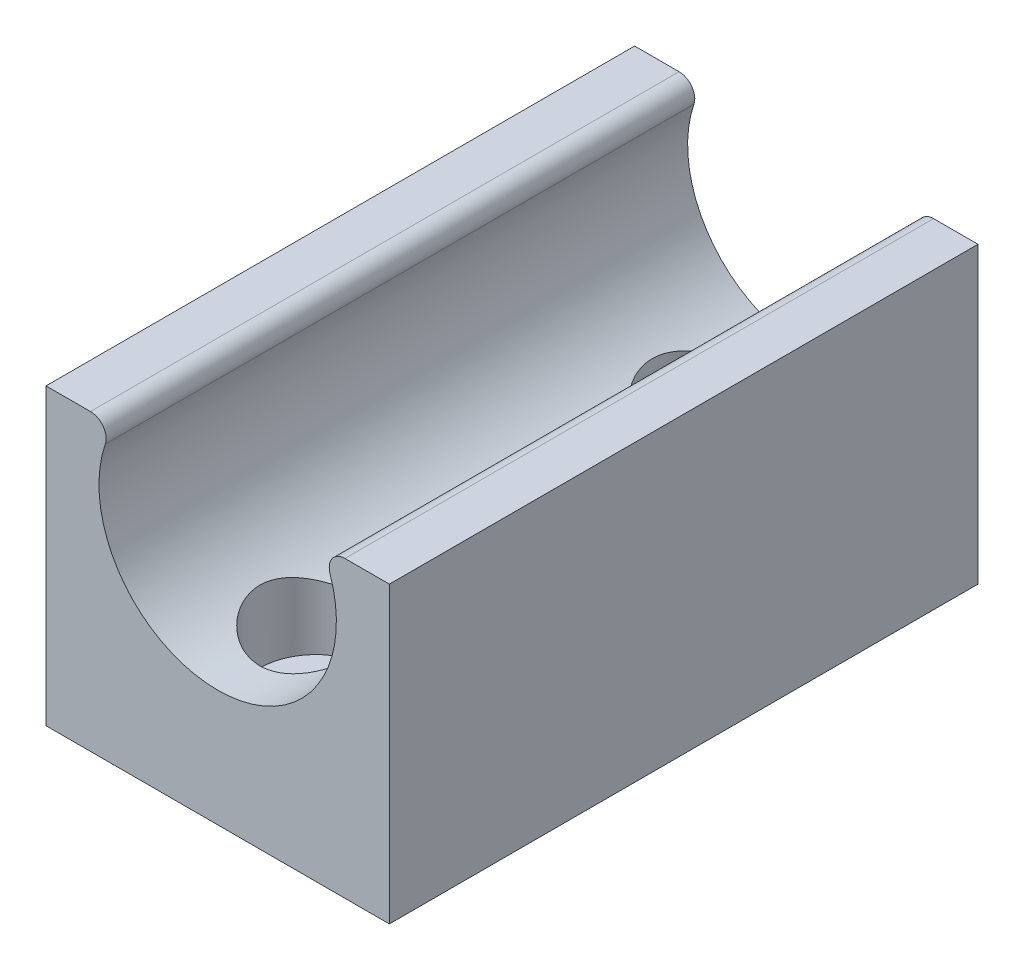
SolidWorks part; units mm, degrees
ref_plane "Front Plane" through (0, 0, 0) normal (0, 0, 1) x (1, 0, 0)
ref_plane "Top Plane" through (0, 0, 0) normal (0, 1, 0) x (1, 0, 0)
ref_plane "Right Plane" through (0, 0, 0) normal (1, 0, 0) x (0, 0, -1)
sketch "Sketch1" plane through (0, 0, 0) normal (0, 0, 1) x (1, 0, 0)
  line L0 (-5.25, 7.5) -> (-8.75, 7.5)
  line L1 (8.75, -7.5) -> (-8.75, -7.5)
  line L2 (8.75, -7.5) -> (8.75, 7.5)
  line L3 (8.75, 7.5) -> (5.25, 7.5)
  line L4 (-8.75, -7.5) -> (-8.75, 7.5)
  line L5 (8.75, -7.5) -> (-8.75, 7.5) construction
  line L6 (8.75, 7.5) -> (-8.75, -7.5) construction
  arc A0 (-5.25, 7.5) -> (5.25, 7.5) centre (0, 4.4933) ccw
  point P0 (0, 0)
  point P7 (0, 0)
  point P10 (0, 0)
  dimension "D1" = 12.1
  dimension "D2" = 3.5
  dimension "D3" = 17.5
  dimension "D4" = 15
extrude "Boss-Extrude1" add sketch "Sketch1" along normal blind 30
fillet "Fillet1" radius 0.8 2 edges at (5.25, 7.5, 15) (-5.25, 7.5, 15)
sketch "Sketch3" plane through (0, 7.5, 0) normal (0, 1, 0) x (1, 0, 0)
  line L0 (6.05, 0) -> (-6.05, 0) construction
  line L1 (-6.05, -30) -> (6.05, -30) construction
  circle A0 centre (0, -5) radius 2.85
  circle A1 centre (0, -25) radius 2.85
  point P9 (0, 0)
  dimension "D1" = 5.7
  dimension "D2" = 5
  dimension "D3" = 5
extrude "Cut-Extrude1" cut sketch "Sketch3" against normal blind 12
sketch "Sketch4" plane through (0, 7.5, 0) normal (0, 1, 0) x (1, 0, 0)
  circle A0 centre (0, -5) radius 1.55
  circle A1 centre (0, -25) radius 1.55
  dimension "D1" = 3.1
  dimension "D2" = 3.1
extrude "Cut-Extrude2" cut sketch "Sketch4" against normal through all
